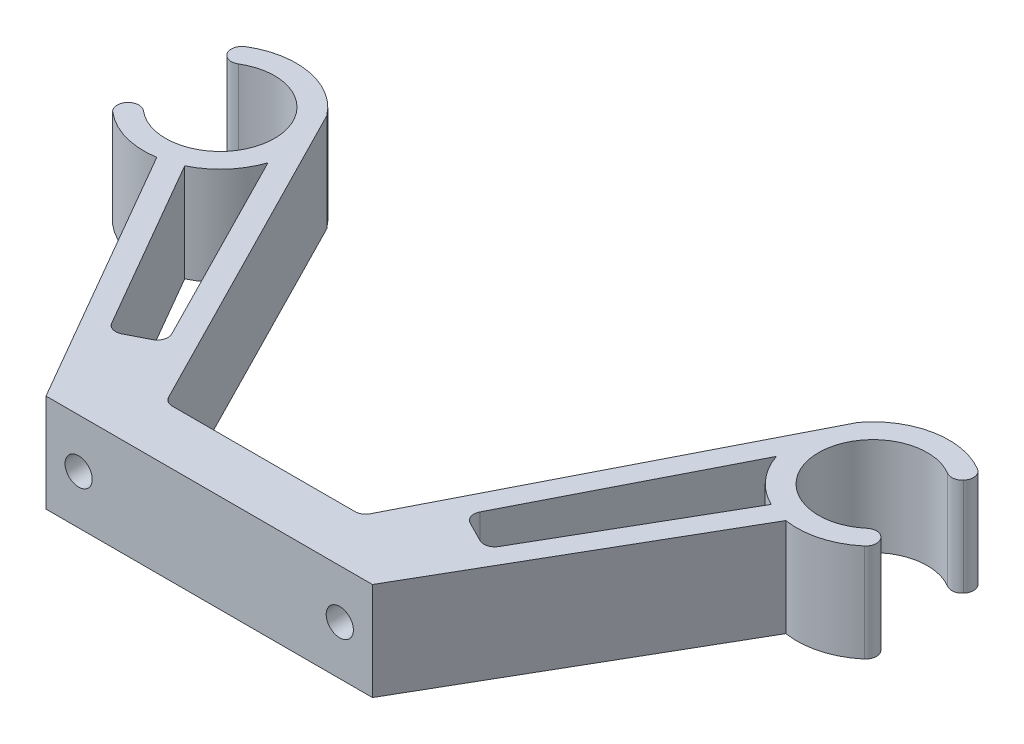
SolidWorks part; units mm, degrees
ref_plane "Front Plane" through (0, 0, 0) normal (0, 0, 1) x (1, 0, 0)
ref_plane "Top Plane" through (0, 0, 0) normal (0, 1, 0) x (1, 0, 0)
ref_plane "Right Plane" through (0, 0, 0) normal (1, 0, 0) x (0, 0, -1)
sketch "Sketch1" plane through (0, 0, 0) normal (0, 1, 0) x (1, 0, 0)
  line L0 (-15, 0) -> (15, 0)
  line L1 (-31.2489, 36.5259) -> (-35.2828, 33.0462) construction
  line L2 (-9, 5) -> (9, 5)
  line L3 (9, 5) -> (24.4085, 35.2113)
  line L8 (15, 0) -> (28.9061, 24.086)
  line L9 (34.5722, 36.3005) -> (33.2658, 34.7861)
  line L10 (33.8302, 27.7861) -> (35.3623, 26.5005)
  line L11 (13.7112, 9.8352) -> (23.3662, 28.7657)
  line L13 (26.9506, 24.6991) -> (17.3094, 8)
  line L14 (17.3094, 8) -> (13.7112, 9.8352)
  line L15 (32.2343, 25.8842) -> (35.4261, 29.688) construction
  line L16 (31.2489, 36.5259) -> (35.2828, 33.0462) construction
  line L17 (0, -17.9193) -> (0, 54.353) construction
  line L18 (-32.2343, 25.8842) -> (-35.4261, 29.688) construction
  line L19 (-17.3094, 8) -> (-13.7112, 9.8352)
  line L20 (-26.9506, 24.6991) -> (-17.3094, 8)
  line L21 (-13.7112, 9.8352) -> (-23.3662, 28.7657)
  line L22 (-33.8302, 27.7861) -> (-35.3623, 26.5005)
  line L23 (-34.5722, 36.3005) -> (-33.2658, 34.7861)
  line L24 (-15, 0) -> (-28.9061, 24.086)
  line L25 (-9, 5) -> (-24.4085, 35.2113)
  arc A1 (33.2658, 34.7861) -> (33.8302, 27.7861) centre (30, 31) ccw
  arc A2 (35.3623, 26.5005) -> (28.9061, 24.086) centre (30, 31) cw
  arc A3 (34.5722, 36.3005) -> (24.4085, 35.2113) centre (30, 31) ccw
  arc A4 (26.9506, 24.6991) -> (23.3662, 28.7657) centre (30, 31) cw
  arc A5 (-26.9506, 24.6991) -> (-23.3662, 28.7657) centre (-30, 31) ccw
  arc A6 (-34.5722, 36.3005) -> (-24.4085, 35.2113) centre (-30, 31) cw
  arc A7 (-35.3623, 26.5005) -> (-28.9061, 24.086) centre (-30, 31) ccw
  arc A8 (-33.2658, 34.7861) -> (-33.8302, 27.7861) centre (-30, 31) cw
  point P6 (0, 0)
  point P39 (0, 5)
  dimension "D3" = 2
  dimension "D4" = 2
  dimension "D5" = 31
  dimension "D6" = 5
  dimension "D7" = 12
  dimension "D12" = 7
  dimension "D15" = 7
  dimension "D1" = 15
  dimension "D2" = 5
  dimension "D8" = 9
  dimension "D9" = 8
  dimension "D10" = 2
  dimension "D11" = 2
  dimension "D13" = 60
  dimension "D16" = 40
  dimension "D17" = 30
extrude "Boss-Extrude1" add sketch "Sketch1" along normal blind 9
fillet "Fillet3" radius 1 14 edges at (-33.2658, 4.5, -34.7861) (-34.5722, 4.5, -36.3005) (-33.8302, 4.5, -27.7861) (-35.3623, 4.5, -26.5005) (-17.3094, 4.5, -8) (-13.7112, 4.5, -9.8352) (17.3094, 4.5, -8) (13.7112, 4.5, -9.8352) (33.2658, 4.5, -34.7861) (34.5722, 4.5, -36.3005) (33.8302, 4.5, -27.7861) (35.3623, 4.5, -26.5005) (-9, 4.5, -5) (9, 4.5, -5)
sketch "Sketch2" plane through (0, 0, 0) normal (0, 0, 1) x (1, 0, 0)
  line L0 (-15, 4.5) -> (15, 4.5) construction
  line L1 (-15, 9) -> (-15, 0) construction
  line L2 (15, 9) -> (15, 0) construction
  line L3 (0, 0) -> (0, 9) construction
  line L4 (-15, 0) -> (15, 0) construction
  line L5 (-15, 9) -> (15, 9) construction
  circle A0 centre (-12, 4.5) radius 1.25
  circle A1 centre (12, 4.5) radius 1.25
  dimension "D1" = 12
  dimension "D2" = 2.5
extrude "Cut-Extrude1" cut sketch "Sketch2" against normal offset from surface (3 mm away) 2 up to face at (0, 4.5, -5)
